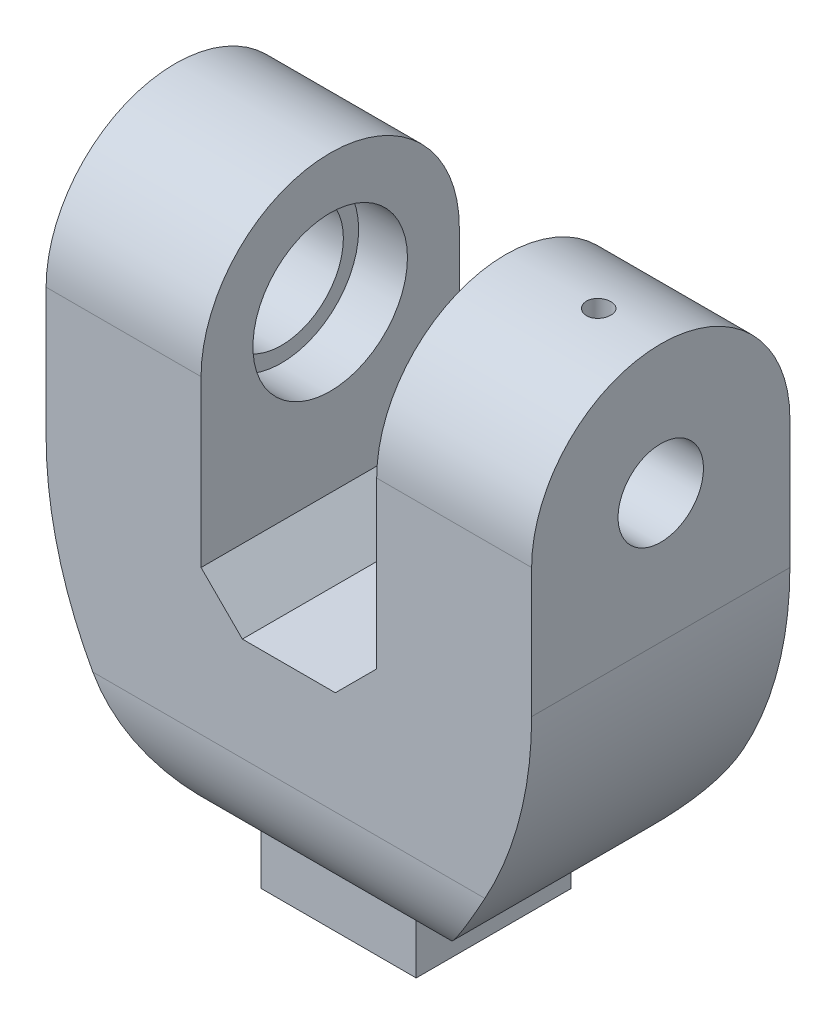
SolidWorks part; units mm, degrees
ref_plane "Front Plane" through (0, 0, 0) normal (0, 0, 1) x (1, 0, 0)
ref_plane "Top Plane" through (0, 0, 0) normal (0, 1, 0) x (1, 0, 0)
ref_plane "Right Plane" through (0, 0, 0) normal (1, 0, 0) x (0, 0, -1)
sketch "Sketch1" plane through (0, 0, 0) normal (1, 0, 0) x (0, 0, -1)
  circle A0 centre (0, 0) radius 3 construction
  circle A1 centre (0, 0) radius 9.5
  circle A2 centre (0, 0) radius 15.875
  dimension "D1" = 6
  dimension "D2" = 19
  dimension "D3" = 31.75
extrude "Boss-Extrude1" add sketch "Sketch1" along normal blind 6
sketch "Sketch2" plane through (0, 0, 0) normal (-1, 0, 0) x (0, 0, 1)
  circle A0 centre (0, 0) radius 9.5 construction
  circle A1 centre (0, 0) radius 15.875
  circle A2 centre (0, 0) radius 15.875
  circle A3 centre (0, 0) radius 9.5
  circle A4 centre (0, 0) radius 7.62
  circle M3 centre (0, 0) radius 15.875
  circle M4 centre (0, 0) radius 9.5
  dimension "D2" = 15.24
  dimension "D1" = 0
extrude "Boss-Extrude2" add sketch "Sketch2" along normal blind 13.05 contours A4 M4 | M3 M4 region at (0, 0, -15.426) region at (0, 0, -9.2313)
ref_plane "Plane1" through (16.795, 0, 0) normal (1, 0, 0) x (0, 0, -1)
mirror "Mirror2" about plane through (16.795, 0, 0) normal (1, 0, 0) of bodies 102
sketch "Sketch3" plane through (6, 0, 0) normal (1, 0, 0) x (0, 0, -1)
  line L0 (-15.875, 0) -> (-15.875, -38.1)
  line L1 (15.875, 0) -> (15.875, -38.1)
  arc A0 (-15.875, -38.1) -> (15.875, -38.1) centre (0, -38.1) ccw
  circle A1 centre (0, 0) radius 15.875
  circle A2 centre (0, 0) radius 15.875
  point P7 (-10.4092, -37.6591)
  point P8 (10.4092, -37.6608)
  circle M2 centre (0, 0) radius 15.875
  dimension "D2" = 38.1
  dimension "D3" = 15.875
  dimension "D1" = 0
extrude "Boss-Extrude3" add sketch "Sketch3" against normal up to surface (19.05 mm away) contours L0 A0 L1 M2 region at (6, -31.5182, 0) up to face at (-13.05, 0, 7.62)
extrude "Boss-Extrude4" add sketch "Sketch3<3>" along normal up to surface (40.64 mm away) from surface contours L0 A0 L1 M2 region at (6, -31.5182, 0) up to face at (46.64, 0, 7.62) starting at face at (27.59, 0, -15.875)
sketch "Sketch3<3>" plane through (6, 0, 0) normal (1, 0, 0) x (0, 0, -1) same geometry as "Sketch3"
sketch "Sketch4" plane through (6, 0, 0) normal (1, 0, 0) x (0, 0, -1)
  line L0 (-15.875, -25.4) -> (15.875, -25.4)
  line L2 (-15.875, 0) -> (-15.875, -38.1)
  line L3 (15.875, -38.1) -> (15.875, 0)
  line L4 (-15.875, 0) -> (-15.875, -38.1)
  line L5 (15.875, -38.1) -> (15.875, 0)
  arc A2 (15.875, 0) -> (-15.875, 0) centre (0, 0) ccw
  arc A3 (-15.875, -38.1) -> (15.875, -38.1) centre (0, -38.1) ccw
  arc A4 (15.875, 0) -> (-15.875, 0) centre (0, 0) ccw
  arc A5 (-15.875, -38.1) -> (15.875, -38.1) centre (0, -38.1) ccw
  line M7 (-15.875, 0) -> (-15.875, -38.1)
  arc M8 (-15.875, -38.1) -> (15.875, -38.1) centre (0, -38.1) ccw
  line M9 (15.875, -38.1) -> (15.875, 0)
  dimension "D2" = 25.4
  dimension "D1" = 0
extrude "Boss-Extrude5" add sketch "Sketch4" along normal up to surface (21.59 mm away) contours L0 M7 M8 M9 region at (6, -38.2335, 0) up to face at (27.59, -19.05, 0)
sketch "Sketch5" plane through (0, 0, 15.875) normal (0, 0, 1) x (1, 0, 0)
  line L0 (6, -15.875) -> (-13.05, -15.875) construction
  line L2 (-13.05, -38.1) -> (-13.05, -53.975) construction
  line L8 (6, 0) -> (-13.05, 0)
  line L9 (-13.05, 0) -> (-13.05, -38.1)
  line L10 (-13.05, -38.1) -> (46.64, -38.1)
  line L11 (46.64, -38.1) -> (46.64, 0)
  line L12 (46.64, 0) -> (27.59, 0)
  line L13 (27.59, 0) -> (27.59, -25.4)
  line L14 (27.59, -25.4) -> (6, -25.4)
  line L15 (6, -25.4) -> (6, 0)
  line L16 (6, 0) -> (-13.05, 0)
  line L17 (-13.05, 0) -> (-13.05, -38.1)
  line L18 (-13.05, -38.1) -> (46.64, -38.1)
  line L19 (46.64, -38.1) -> (46.64, 0)
  line L20 (46.64, 0) -> (27.59, 0)
  line L21 (27.59, 0) -> (27.59, -25.4)
  line L22 (27.59, -25.4) -> (6, -25.4)
  line L23 (6, -25.4) -> (6, 0)
  line L25 (-13.05, -38.1) -> (-13.05, -53.975)
  line L26 (-13.05, -53.975) -> (46.64, -53.975)
  line L27 (46.64, -53.975) -> (46.64, -38.1)
  line L28 (-13.05, -15.875) -> (7.27, -53.975)
  line L29 (46.64, -15.875) -> (26.32, -53.975)
  line L30 (-13.05, -53.975) -> (46.64, -53.975) construction
  line L31 (16.795, -17.4625) -> (16.795, 17.4625) construction
  arc A0 (-13.05, -15.875) -> (7.27, -53.975) centre (32.8287, -15.875) ccw
  arc A1 (46.64, -15.875) -> (26.32, -53.975) centre (0.7613, -15.875) cw
  point P16 (7.6951, -53.975)
  line M14 (-13.05, -38.1) -> (46.64, -38.1)
  line M15 (46.64, -38.1) -> (46.64, 0)
  dimension "D2" = 15.875
  dimension "D3" = 19.05
  dimension "D1" = 0
extrude "Cut-Extrude1" cut sketch "Sketch5" against normal through all contours L28 L25 L26 M14 | L28 L17 M14 | L29 L26 L27 M14 | L29 M15 M14 region at (-11.3474, -32.6157, 15.875) region at (-6.3907, -47.6285, 15.875) region at (44.9374, -32.6157, 15.875) region at (39.9807, -47.6285, 15.875)
sketch "Sketch9" plane through (0, -25.4, 0) normal (0, 1, 0) x (1, 0, 0)
  line L0 (5.7854, 0) -> (27.3575, 0) construction
  line L1 (16.795, 15.875) -> (16.795, -15.875) construction
  line L2 (27.59, 15.875) -> (6, 15.875) construction
  line L4 (27.59, -15.875) -> (27.59, 15.875)
  line L5 (27.59, 15.875) -> (6, 15.875)
  line L6 (6, 15.875) -> (6, -15.875)
  line L7 (6, -15.875) -> (27.59, -15.875)
  line L8 (27.59, -15.875) -> (27.59, 15.875)
  line L9 (27.59, 15.875) -> (6, 15.875)
  line L10 (6, 15.875) -> (6, -15.875)
  line L11 (6, -15.875) -> (27.59, -15.875)
  line L12 (7.0465, -9.525) -> (26.0965, -9.525)
  line L13 (7.0465, -9.525) -> (7.0465, 9.525)
  line L14 (7.0465, 9.525) -> (26.0965, 9.525)
  line L15 (26.0965, -9.525) -> (26.0965, 9.525)
  line L16 (7.0465, -9.525) -> (26.0965, 9.525) construction
  line L17 (7.0465, 9.525) -> (26.0965, -9.525) construction
  point P12 (16.5715, 0)
  dimension "D2" = 19.05
  dimension "D1" = 0
extrude "Boss-Extrude8" add sketch "Sketch9" against normal blind 31.75 contours L12 L15 L14 L13 region at (16.5715, -25.4, 0)
chamfer "Chamfer1" distance 5.08 angle 45 2 edges at (27.59, -25.4, 0) (6, -25.4, 0)
sketch "Sketch6" plane through (46.64, 0, 0) normal (1, 0, 0) x (0, 0, -1)
  line L3 (-15.875, 0) -> (-15.875, -15.875)
  line L4 (-15.875, -15.875) -> (15.875, -15.875)
  line L5 (15.875, -15.875) -> (15.875, 0)
  line L6 (-15.875, 0) -> (-15.875, -15.875)
  line L8 (15.875, -15.875) -> (15.875, 0)
  line L9 (-15.875, -15.875) -> (15.875, -15.875)
  circle A0 centre (0, 0) radius 7.62 construction
  arc A1 (15.875, 0) -> (-15.875, 0) centre (0, 0) ccw
  arc A2 (15.875, 0) -> (-15.875, 0) centre (0, 0) ccw
  circle A3 centre (0, 0) radius 7.62
  circle A4 centre (0, 0) radius 5.25
  circle M14 centre (0, 0) radius 7.62
  dimension "D2" = 10.5
  dimension "D1" = 0
extrude "Boss-Extrude6" add sketch "Sketch6" against normal up to surface (13.05 mm away) contours A4 M14 region at (46.64, 0, 7.4045) up to face at (33.59, 0, 7.62)
sketch "Sketch7" plane through (-13.05, 0, 0) normal (-1, 0, 0) x (0, 0, 1)
  line L0 (0, 0) -> (0, 12.7) construction
  line L3 (-15.875, 0) -> (-15.875, -15.875)
  line L4 (-15.875, -15.875) -> (15.875, -15.875)
  line L5 (15.875, -15.875) -> (15.875, 0)
  line L6 (-15.875, 0) -> (-15.875, -15.875)
  line L8 (15.875, -15.875) -> (15.875, 0)
  line L10 (-15.875, -15.875) -> (15.875, -15.875)
  circle A0 centre (0, 0) radius 7.62 construction
  arc A1 (15.875, 0) -> (-15.875, 0) centre (0, 0) ccw
  arc A2 (15.875, 0) -> (-15.875, 0) centre (0, 0) ccw
  circle A3 centre (0, 0) radius 7.62
  circle A4 centre (0, 12.7) radius 1.5
  circle A5 centre (0, -12.7) radius 1.5
  point P8 (0, 0)
  point P15 (0, -12.7)
  dimension "D2" = 3
  dimension "D5" = 3
  dimension "D3" = 12.7
  dimension "D4" = 12.7
  dimension "D1" = 0
extrude "Cut-Extrude2" cut sketch "Sketch7" against normal blind 12.7 contours A4 | A5 region at (-13.05, 12.7, 0) region at (-13.05, -12.7, 0)
ref_plane "Plane2" through (0, 15.875, 0) normal (0, 1, 0) x (1, 0, 0)
sketch "Sketch8" plane through (0, 15.875, 0) normal (0, 1, 0) x (1, 0, 0)
  line L0 (46.64, -15.875) -> (46.64, 15.875) construction
  circle A0 centre (39.02, 0) radius 1.5
  point P2 (38.1268, 0)
  point P5 (0, 0)
  dimension "D1" = 3
  dimension "D2" = 7.62
extrude "Cut-Extrude3" cut sketch "Sketch8" against normal up to surface (10.8438 mm away) up to face at (33.59, 0, -5.25)
